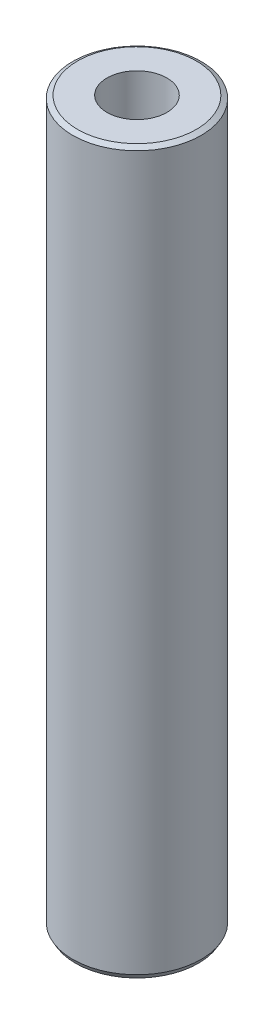
SolidWorks part; units mm, degrees
ref_plane "Front Plane" through (0, 0, 0) normal (0, 0, 1) x (1, 0, 0)
ref_plane "Top Plane" through (0, 0, 0) normal (0, 1, 0) x (1, 0, 0)
ref_plane "Right Plane" through (0, 0, 0) normal (1, 0, 0) x (0, 0, -1)
sketch "Sketch1" plane through (0, 0, 0) normal (0, 1, 0) x (1, 0, 0)
  circle A0 centre (0, 0) radius 50
  dimension "SHAFT_OD" = 100
extrude "Boss-Extrude1" add sketch "Sketch1" along normal blind 561.8995
sketch "Sketch2" plane through (0, 0, 0) normal (0, 1, 0) x (1, 0, 0)
  circle A0 centre (0, 0) radius 23.3194
  dimension "BORE_D" = 46.6388
extrude "Cut-Extrude1" cut sketch "Sketch2" along normal through all
chamfer "Chamfer1" distance 2.1594 angle 60 2 edges at (0, 561.8995, 50) (0, 0, 50) first distance on face at (0, 561.8995, 50) first distance on face at (0, 0, 23.3194)
